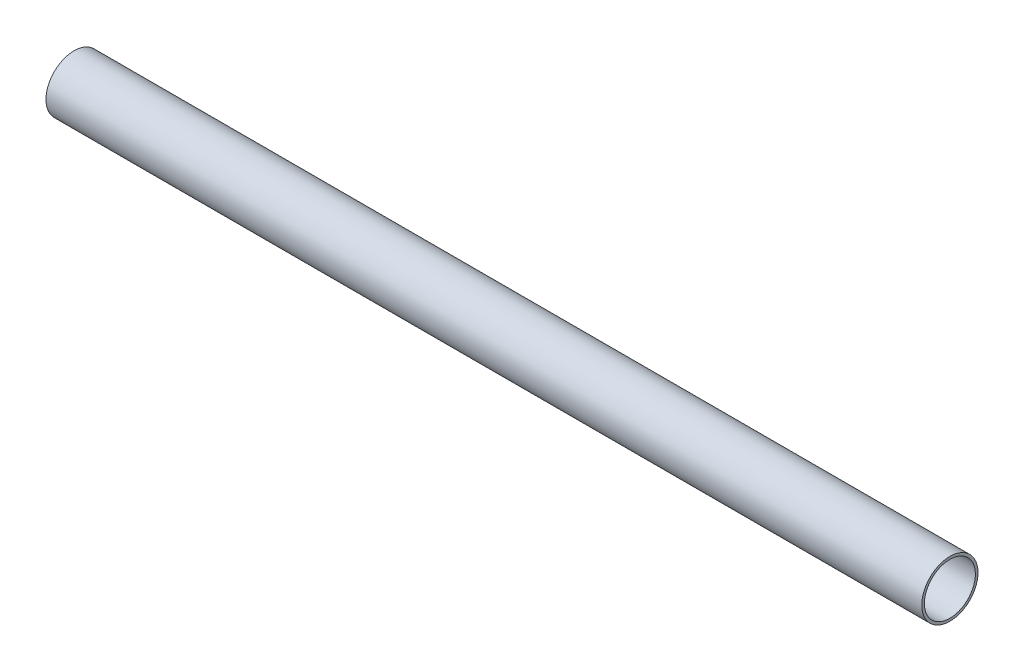
SolidWorks part; units mm, degrees
ref_plane "Front Plane" through (0, 0, 0) normal (0, 0, 1) x (1, 0, 0)
ref_plane "Top Plane" through (0, 0, 0) normal (0, 1, 0) x (1, 0, 0)
ref_plane "Right Plane" through (0, 0, 0) normal (1, 0, 0) x (0, 0, -1)
sketch "Sketch1" plane through (0, 0, 0) normal (1, 0, 0) x (0, 0, -1)
  circle A0 centre (0, 0) radius 9.525
  circle A1 centre (0, 0) radius 8.636
  dimension "D1" = 19.05
  dimension "D2" = 17.272
extrude "Boss-Extrude1" add sketch "Sketch1" along normal up to surface (296.6159 mm away)
equation "\"D1@Boss-Extrude1\"=12.489-2*(.25+3/8+.312/2)"
